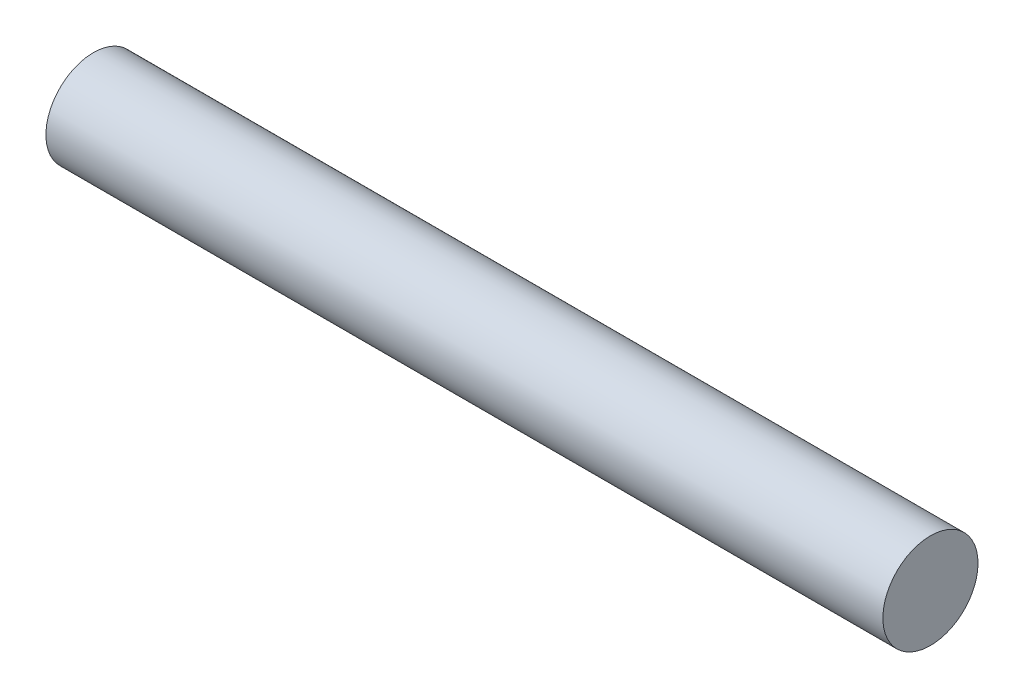
SolidWorks part; units mm, degrees
ref_plane "Front Plane" through (0, 0, 0) normal (0, 0, 1) x (1, 0, 0)
ref_plane "Top Plane" through (0, 0, 0) normal (0, 1, 0) x (1, 0, 0)
ref_plane "Right Plane" through (0, 0, 0) normal (1, 0, 0) x (0, 0, -1)
ref_axis "X" through (-88.99, 0, 0) along (1, 0, 0)
ref_axis "Y" through (0, 0, -88.99) along (0, 0, 1)
ref_axis "Z" through (0, 55, 0) along (0, -1, 0)
sketch "Sketch1" plane through (0, 0, 0) normal (0, 0, 1) x (1, 0, 0)
  line L0 (0, 0) -> (-28.2258, 0) construction
  line L1 (0, 0) -> (0, 7.5)
  line L2 (0, 7.5) -> (132, 7.5)
  line L3 (132, 7.5) -> (132, 0)
  line L4 (132, 0) -> (0, 0)
  dimension "D1" = 15
  dimension "D2" = 132
revolve "Revolve1" add sketch "Sketch1" angle 360 about L0
ref_plane "Plane1" through (66, 0, 0) normal (1, 0, 0) x (0, 0, -1)
